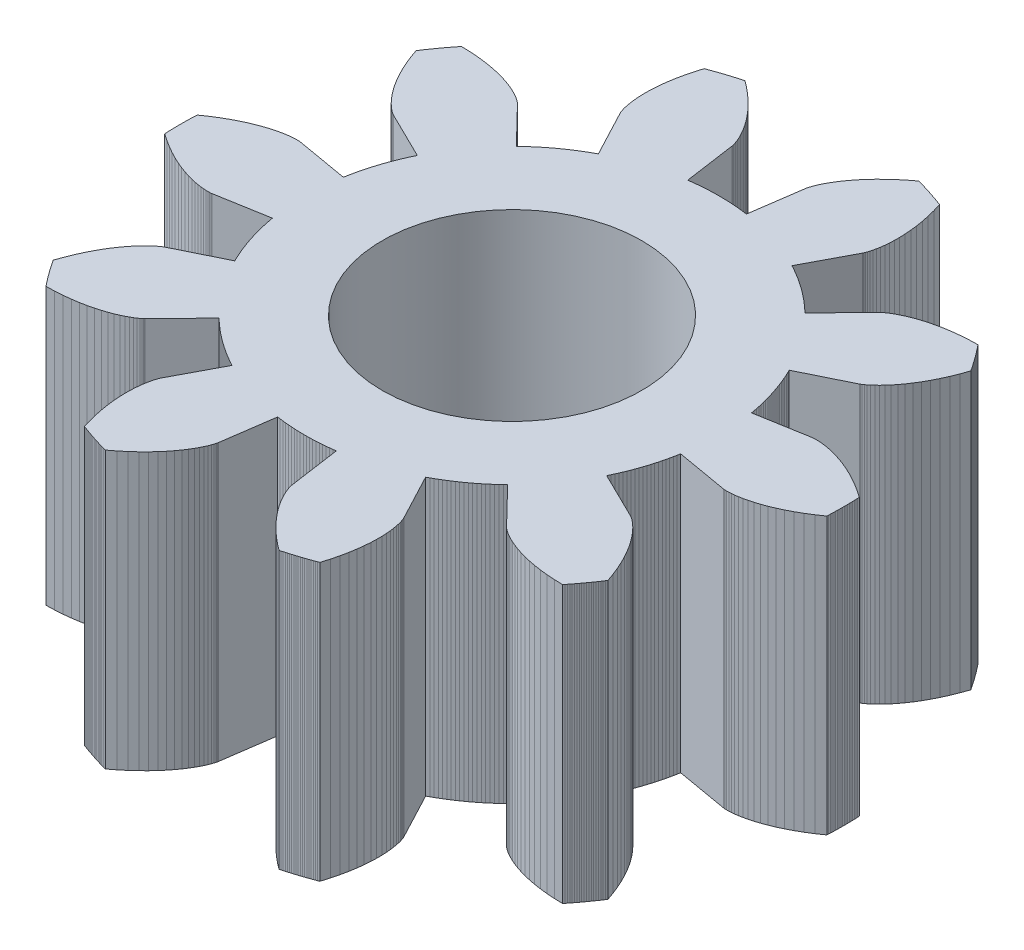
SolidWorks part; units mm, degrees
ref_plane "Front Plane" through (0, 0, 0) normal (0, 0, 1) x (1, 0, 0)
ref_plane "Top Plane" through (0, 0, 0) normal (0, 1, 0) x (1, 0, 0)
ref_plane "Right Plane" through (0, 0, 0) normal (1, 0, 0) x (0, 0, -1)
sketch "Sketch1" plane through (0, 0, 0) normal (0, 1, 0) x (1, 0, 0)
  line L0 (3.6947, -0.6418) -> (4.6291, -0.8041)
  line L1 (4.6291, -0.8041) -> (4.6332, -0.8047)
  line L2 (4.6332, -0.8047) -> (4.6455, -0.806)
  line L3 (4.6455, -0.806) -> (4.6659, -0.8073)
  line L4 (4.6659, -0.8073) -> (4.6947, -0.8081)
  line L5 (4.6947, -0.8081) -> (4.7316, -0.8074)
  line L6 (4.7316, -0.8074) -> (4.7767, -0.8048)
  line L7 (4.7767, -0.8048) -> (4.8297, -0.7994)
  line L8 (4.8297, -0.7994) -> (4.8907, -0.7907)
  line L9 (4.8907, -0.7907) -> (4.9593, -0.778)
  line L10 (4.9593, -0.778) -> (5.0353, -0.7605)
  line L11 (5.0353, -0.7605) -> (5.1184, -0.7378)
  line L12 (5.1184, -0.7378) -> (5.2084, -0.7091)
  line L13 (5.2084, -0.7091) -> (5.3047, -0.6738)
  line L14 (5.3047, -0.6738) -> (5.4071, -0.6314)
  line L15 (5.4071, -0.6314) -> (5.5151, -0.5813)
  line L16 (5.5151, -0.5813) -> (5.6282, -0.523)
  line L17 (5.6282, -0.523) -> (5.7459, -0.456)
  line L18 (5.7459, -0.456) -> (5.8676, -0.3797)
  line L19 (5.8676, -0.3797) -> (5.9928, -0.2937)
  line L20 (5.9928, -0.2937) -> (5.9942, -0.2628)
  line L21 (5.9942, -0.2628) -> (5.9955, -0.2319)
  line L22 (5.9955, -0.2319) -> (5.9966, -0.201)
  line L23 (5.9966, -0.201) -> (5.9976, -0.1701)
  line L24 (5.9976, -0.1701) -> (5.9984, -0.1392)
  line L25 (5.9984, -0.1392) -> (5.999, -0.1083)
  line L26 (5.999, -0.1083) -> (5.9995, -0.0773)
  line L27 (5.9995, -0.0773) -> (5.9998, -0.0464)
  line L28 (5.9998, -0.0464) -> (6, -0.0155)
  line L29 (6, -0.0155) -> (6, 0.0155)
  line L30 (6, 0.0155) -> (5.9998, 0.0464)
  line L31 (5.9998, 0.0464) -> (5.9995, 0.0773)
  line L32 (5.9995, 0.0773) -> (5.999, 0.1083)
  line L33 (5.999, 0.1083) -> (5.9984, 0.1392)
  line L34 (5.9984, 0.1392) -> (5.9976, 0.1701)
  line L35 (5.9976, 0.1701) -> (5.9966, 0.201)
  line L36 (5.9966, 0.201) -> (5.9955, 0.2319)
  line L37 (5.9955, 0.2319) -> (5.9942, 0.2628)
  line L38 (5.9942, 0.2628) -> (5.9928, 0.2937)
  line L39 (5.9928, 0.2937) -> (5.8676, 0.3797)
  line L40 (5.8676, 0.3797) -> (5.7459, 0.456)
  line L41 (5.7459, 0.456) -> (5.6282, 0.523)
  line L42 (5.6282, 0.523) -> (5.5151, 0.5813)
  line L43 (5.5151, 0.5813) -> (5.4071, 0.6314)
  line L44 (5.4071, 0.6314) -> (5.3047, 0.6738)
  line L45 (5.3047, 0.6738) -> (5.2084, 0.7091)
  line L46 (5.2084, 0.7091) -> (5.1184, 0.7378)
  line L47 (5.1184, 0.7378) -> (5.0353, 0.7605)
  line L48 (5.0353, 0.7605) -> (4.9593, 0.778)
  line L49 (4.9593, 0.778) -> (4.8907, 0.7907)
  line L50 (4.8907, 0.7907) -> (4.8297, 0.7994)
  line L51 (4.8297, 0.7994) -> (4.7767, 0.8048)
  line L52 (4.7767, 0.8048) -> (4.7316, 0.8074)
  line L53 (4.7316, 0.8074) -> (4.6947, 0.8081)
  line L54 (4.6947, 0.8081) -> (4.6659, 0.8073)
  line L55 (4.6659, 0.8073) -> (4.6455, 0.806)
  line L56 (4.6455, 0.806) -> (4.6332, 0.8047)
  line L57 (4.6332, 0.8047) -> (4.6291, 0.8041)
  line L58 (4.6291, 0.8041) -> (3.6947, 0.6418)
  line L59 (3.6947, 0.6418) -> (3.6847, 0.697)
  line L60 (3.6847, 0.697) -> (3.6738, 0.752)
  line L61 (3.6738, 0.752) -> (3.6621, 0.8069)
  line L62 (3.6621, 0.8069) -> (3.6497, 0.8617)
  line L63 (3.6497, 0.8617) -> (3.6364, 0.9162)
  line L64 (3.6364, 0.9162) -> (3.6222, 0.9705)
  line L65 (3.6222, 0.9705) -> (3.6073, 1.0246)
  line L66 (3.6073, 1.0246) -> (3.5916, 1.0785)
  line L67 (3.5916, 1.0785) -> (3.575, 1.1321)
  line L68 (3.575, 1.1321) -> (3.5577, 1.1855)
  line L69 (3.5577, 1.1855) -> (3.5396, 1.2386)
  line L70 (3.5396, 1.2386) -> (3.5206, 1.2914)
  line L71 (3.5206, 1.2914) -> (3.5009, 1.344)
  line L72 (3.5009, 1.344) -> (3.4804, 1.3962)
  line L73 (3.4804, 1.3962) -> (3.4591, 1.4481)
  line L74 (3.4591, 1.4481) -> (3.4371, 1.4997)
  line L75 (3.4371, 1.4997) -> (3.4142, 1.551)
  line L76 (3.4142, 1.551) -> (3.3906, 1.6019)
  line L77 (3.3906, 1.6019) -> (3.3663, 1.6525)
  line L78 (3.3663, 1.6525) -> (4.2177, 2.0704)
  line L79 (4.2177, 2.0704) -> (4.2213, 2.0723)
  line L80 (4.2213, 2.0723) -> (4.232, 2.0785)
  line L81 (4.232, 2.0785) -> (4.2494, 2.0894)
  line L82 (4.2494, 2.0894) -> (4.273, 2.1057)
  line L83 (4.273, 2.1057) -> (4.3025, 2.1279)
  line L84 (4.3025, 2.1279) -> (4.3374, 2.1566)
  line L85 (4.3374, 2.1566) -> (4.3773, 2.1921)
  line L86 (4.3773, 2.1921) -> (4.4214, 2.235)
  line L87 (4.4214, 2.235) -> (4.4694, 2.2856)
  line L88 (4.4694, 2.2856) -> (4.5207, 2.3444)
  line L89 (4.5207, 2.3444) -> (4.5746, 2.4117)
  line L90 (4.5746, 2.4117) -> (4.6304, 2.4877)
  line L91 (4.6304, 2.4877) -> (4.6877, 2.5729)
  line L92 (4.6877, 2.5729) -> (4.7456, 2.6674)
  line L93 (4.7456, 2.6674) -> (4.8035, 2.7714)
  line L94 (4.8035, 2.7714) -> (4.8607, 2.885)
  line L95 (4.8607, 2.885) -> (4.9165, 3.0085)
  line L96 (4.9165, 3.0085) -> (4.9702, 3.1417)
  line L97 (4.9702, 3.1417) -> (5.0209, 3.2848)
  line L98 (5.0209, 3.2848) -> (5.0039, 3.3107)
  line L99 (5.0039, 3.3107) -> (4.9868, 3.3364)
  line L100 (4.9868, 3.3364) -> (4.9695, 3.3621)
  line L101 (4.9695, 3.3621) -> (4.9521, 3.3877)
  line L102 (4.9521, 3.3877) -> (4.9346, 3.4132)
  line L103 (4.9346, 3.4132) -> (4.9169, 3.4386)
  line L104 (4.9169, 3.4386) -> (4.8992, 3.4639)
  line L105 (4.8992, 3.4639) -> (4.8812, 3.4891)
  line L106 (4.8812, 3.4891) -> (4.8632, 3.5142)
  line L107 (4.8632, 3.5142) -> (4.845, 3.5392)
  line L108 (4.845, 3.5392) -> (4.8267, 3.5641)
  line L109 (4.8267, 3.5641) -> (4.8082, 3.589)
  line L110 (4.8082, 3.589) -> (4.7897, 3.6137)
  line L111 (4.7897, 3.6137) -> (4.771, 3.6384)
  line L112 (4.771, 3.6384) -> (4.7522, 3.6629)
  line L113 (4.7522, 3.6629) -> (4.7332, 3.6874)
  line L114 (4.7332, 3.6874) -> (4.7141, 3.7117)
  line L115 (4.7141, 3.7117) -> (4.6949, 3.736)
  line L116 (4.6949, 3.736) -> (4.6756, 3.7601)
  line L117 (4.6756, 3.7601) -> (4.5238, 3.7561)
  line L118 (4.5238, 3.7561) -> (4.3805, 3.7462)
  line L119 (4.3805, 3.7462) -> (4.2459, 3.7313)
  line L120 (4.2459, 3.7313) -> (4.1201, 3.712)
  line L121 (4.1201, 3.712) -> (4.0033, 3.6891)
  line L122 (4.0033, 3.6891) -> (3.8956, 3.6632)
  line L123 (3.8956, 3.6632) -> (3.7969, 3.6351)
  line L124 (3.7969, 3.6351) -> (3.7072, 3.6054)
  line L125 (3.7072, 3.6054) -> (3.6266, 3.575)
  line L126 (3.6266, 3.575) -> (3.5549, 3.5444)
  line L127 (3.5549, 3.5444) -> (3.4919, 3.5144)
  line L128 (3.4919, 3.5144) -> (3.4374, 3.4856)
  line L129 (3.4374, 3.4856) -> (3.3914, 3.4587)
  line L130 (3.3914, 3.4587) -> (3.3533, 3.4344)
  line L131 (3.3533, 3.4344) -> (3.3231, 3.4132)
  line L132 (3.3231, 3.4132) -> (3.3003, 3.3957)
  line L133 (3.3003, 3.3957) -> (3.2845, 3.3826)
  line L134 (3.2845, 3.3826) -> (3.2754, 3.3743)
  line L135 (3.2754, 3.3743) -> (3.2724, 3.3715)
  line L136 (3.2724, 3.3715) -> (2.6118, 2.6909)
  line L137 (2.6118, 2.6909) -> (2.5713, 2.7297)
  line L138 (2.5713, 2.7297) -> (2.5301, 2.7678)
  line L139 (2.5301, 2.7678) -> (2.4884, 2.8054)
  line L140 (2.4884, 2.8054) -> (2.4462, 2.8423)
  line L141 (2.4462, 2.8423) -> (2.4034, 2.8786)
  line L142 (2.4034, 2.8786) -> (2.36, 2.9142)
  line L143 (2.36, 2.9142) -> (2.3161, 2.9492)
  line L144 (2.3161, 2.9492) -> (2.2717, 2.9836)
  line L145 (2.2717, 2.9836) -> (2.2268, 3.0172)
  line L146 (2.2268, 3.0172) -> (2.1814, 3.0502)
  line L147 (2.1814, 3.0502) -> (2.1355, 3.0825)
  line L148 (2.1355, 3.0825) -> (2.0892, 3.1141)
  line L149 (2.0892, 3.1141) -> (2.0423, 3.1451)
  line L150 (2.0423, 3.1451) -> (1.995, 3.1753)
  line L151 (1.995, 3.1753) -> (1.9473, 3.2048)
  line L152 (1.9473, 3.2048) -> (1.8991, 3.2336)
  line L153 (1.8991, 3.2336) -> (1.8505, 3.2616)
  line L154 (1.8505, 3.2616) -> (1.8015, 3.2889)
  line L155 (1.8015, 3.2889) -> (1.7521, 3.3155)
  line L156 (1.7521, 3.3155) -> (2.1952, 4.1541)
  line L157 (2.1952, 4.1541) -> (2.197, 4.1578)
  line L158 (2.197, 4.1578) -> (2.2021, 4.169)
  line L159 (2.2021, 4.169) -> (2.2097, 4.1881)
  line L160 (2.2097, 4.1881) -> (2.2192, 4.2152)
  line L161 (2.2192, 4.2152) -> (2.23, 4.2505)
  line L162 (2.23, 4.2505) -> (2.2415, 4.2942)
  line L163 (2.2415, 4.2942) -> (2.2528, 4.3463)
  line L164 (2.2528, 4.3463) -> (2.2633, 4.407)
  line L165 (2.2633, 4.407) -> (2.2724, 4.4762)
  line L166 (2.2724, 4.4762) -> (2.2793, 4.5538)
  line L167 (2.2793, 4.5538) -> (2.2834, 4.6399)
  line L168 (2.2834, 4.6399) -> (2.2838, 4.7343)
  line L169 (2.2838, 4.7343) -> (2.2801, 4.8369)
  line L170 (2.2801, 4.8369) -> (2.2714, 4.9474)
  line L171 (2.2714, 4.9474) -> (2.2571, 5.0655)
  line L172 (2.2571, 5.0655) -> (2.2366, 5.1911)
  line L173 (2.2366, 5.1911) -> (2.2092, 5.3237)
  line L174 (2.2092, 5.3237) -> (2.1743, 5.4631)
  line L175 (2.1743, 5.4631) -> (2.1312, 5.6087)
  line L176 (2.1312, 5.6087) -> (2.1023, 5.6196)
  line L177 (2.1023, 5.6196) -> (2.0733, 5.6304)
  line L178 (2.0733, 5.6304) -> (2.0442, 5.641)
  line L179 (2.0442, 5.641) -> (2.0151, 5.6515)
  line L180 (2.0151, 5.6515) -> (1.986, 5.6618)
  line L181 (1.986, 5.6618) -> (1.9568, 5.672)
  line L182 (1.9568, 5.672) -> (1.9275, 5.682)
  line L183 (1.9275, 5.682) -> (1.8982, 5.6918)
  line L184 (1.8982, 5.6918) -> (1.8688, 5.7015)
  line L185 (1.8688, 5.7015) -> (1.8394, 5.7111)
  line L186 (1.8394, 5.7111) -> (1.8099, 5.7205)
  line L187 (1.8099, 5.7205) -> (1.7804, 5.7298)
  line L188 (1.7804, 5.7298) -> (1.7508, 5.7389)
  line L189 (1.7508, 5.7389) -> (1.7212, 5.7478)
  line L190 (1.7212, 5.7478) -> (1.6916, 5.7566)
  line L191 (1.6916, 5.7566) -> (1.6619, 5.7653)
  line L192 (1.6619, 5.7653) -> (1.6321, 5.7737)
  line L193 (1.6321, 5.7737) -> (1.6023, 5.7821)
  line L194 (1.6023, 5.7821) -> (1.5725, 5.7903)
  line L195 (1.5725, 5.7903) -> (1.4521, 5.6977)
  line L196 (1.4521, 5.6977) -> (1.3419, 5.6055)
  line L197 (1.3419, 5.6055) -> (1.2418, 5.5143)
  line L198 (1.2418, 5.5143) -> (1.1514, 5.4248)
  line L199 (1.1514, 5.4248) -> (1.0704, 5.3376)
  line L200 (1.0704, 5.3376) -> (0.9984, 5.2533)
  line L201 (0.9984, 5.2533) -> (0.9351, 5.1726)
  line L202 (0.9351, 5.1726) -> (0.88, 5.0959)
  line L203 (0.88, 5.0959) -> (0.8327, 5.0239)
  line L204 (0.8327, 5.0239) -> (0.7926, 4.957)
  line L205 (0.7926, 4.957) -> (0.7593, 4.8957)
  line L206 (0.7593, 4.8957) -> (0.7322, 4.8404)
  line L207 (0.7322, 4.8404) -> (0.7107, 4.7916)
  line L208 (0.7107, 4.7916) -> (0.6942, 4.7495)
  line L209 (0.6942, 4.7495) -> (0.6822, 4.7146)
  line L210 (0.6822, 4.7146) -> (0.674, 4.687)
  line L211 (0.674, 4.687) -> (0.669, 4.6672)
  line L212 (0.669, 4.6672) -> (0.6665, 4.6551)
  line L213 (0.6665, 4.6551) -> (0.6658, 4.6511)
  line L214 (0.6658, 4.6511) -> (0.5314, 3.7122)
  line L215 (0.5314, 3.7122) -> (0.4757, 3.7197)
  line L216 (0.4757, 3.7197) -> (0.42, 3.7264)
  line L217 (0.42, 3.7264) -> (0.3642, 3.7323)
  line L218 (0.3642, 3.7323) -> (0.3083, 3.7373)
  line L219 (0.3083, 3.7373) -> (0.2524, 3.7415)
  line L220 (0.2524, 3.7415) -> (0.1963, 3.7449)
  line L221 (0.1963, 3.7449) -> (0.1403, 3.7474)
  line L222 (0.1403, 3.7474) -> (0.0842, 3.7491)
  line L223 (0.0842, 3.7491) -> (0.0281, 3.7499)
  line L224 (0.0281, 3.7499) -> (-0.0281, 3.7499)
  line L225 (-0.0281, 3.7499) -> (-0.0842, 3.7491)
  line L226 (-0.0842, 3.7491) -> (-0.1403, 3.7474)
  line L227 (-0.1403, 3.7474) -> (-0.1963, 3.7449)
  line L228 (-0.1963, 3.7449) -> (-0.2524, 3.7415)
  line L229 (-0.2524, 3.7415) -> (-0.3083, 3.7373)
  line L230 (-0.3083, 3.7373) -> (-0.3642, 3.7323)
  line L231 (-0.3642, 3.7323) -> (-0.42, 3.7264)
  line L232 (-0.42, 3.7264) -> (-0.4757, 3.7197)
  line L233 (-0.4757, 3.7197) -> (-0.5314, 3.7122)
  line L234 (-0.5314, 3.7122) -> (-0.6658, 4.6511)
  line L235 (-0.6658, 4.6511) -> (-0.6665, 4.6551)
  line L236 (-0.6665, 4.6551) -> (-0.669, 4.6672)
  line L237 (-0.669, 4.6672) -> (-0.674, 4.687)
  line L238 (-0.674, 4.687) -> (-0.6822, 4.7146)
  line L239 (-0.6822, 4.7146) -> (-0.6942, 4.7495)
  line L240 (-0.6942, 4.7495) -> (-0.7107, 4.7916)
  line L241 (-0.7107, 4.7916) -> (-0.7322, 4.8404)
  line L242 (-0.7322, 4.8404) -> (-0.7593, 4.8957)
  line L243 (-0.7593, 4.8957) -> (-0.7926, 4.957)
  line L244 (-0.7926, 4.957) -> (-0.8327, 5.0239)
  line L245 (-0.8327, 5.0239) -> (-0.88, 5.0959)
  line L246 (-0.88, 5.0959) -> (-0.9351, 5.1726)
  line L247 (-0.9351, 5.1726) -> (-0.9984, 5.2533)
  line L248 (-0.9984, 5.2533) -> (-1.0704, 5.3376)
  line L249 (-1.0704, 5.3376) -> (-1.1514, 5.4248)
  line L250 (-1.1514, 5.4248) -> (-1.2418, 5.5143)
  line L251 (-1.2418, 5.5143) -> (-1.3419, 5.6055)
  line L252 (-1.3419, 5.6055) -> (-1.4521, 5.6977)
  line L253 (-1.4521, 5.6977) -> (-1.5725, 5.7903)
  line L254 (-1.5725, 5.7903) -> (-1.6023, 5.7821)
  line L255 (-1.6023, 5.7821) -> (-1.6321, 5.7737)
  line L256 (-1.6321, 5.7737) -> (-1.6619, 5.7653)
  line L257 (-1.6619, 5.7653) -> (-1.6916, 5.7566)
  line L258 (-1.6916, 5.7566) -> (-1.7212, 5.7478)
  line L259 (-1.7212, 5.7478) -> (-1.7508, 5.7389)
  line L260 (-1.7508, 5.7389) -> (-1.7804, 5.7298)
  line L261 (-1.7804, 5.7298) -> (-1.8099, 5.7205)
  line L262 (-1.8099, 5.7205) -> (-1.8394, 5.7111)
  line L263 (-1.8394, 5.7111) -> (-1.8688, 5.7015)
  line L264 (-1.8688, 5.7015) -> (-1.8982, 5.6918)
  line L265 (-1.8982, 5.6918) -> (-1.9275, 5.682)
  line L266 (-1.9275, 5.682) -> (-1.9568, 5.672)
  line L267 (-1.9568, 5.672) -> (-1.986, 5.6618)
  line L268 (-1.986, 5.6618) -> (-2.0151, 5.6515)
  line L269 (-2.0151, 5.6515) -> (-2.0442, 5.641)
  line L270 (-2.0442, 5.641) -> (-2.0733, 5.6304)
  line L271 (-2.0733, 5.6304) -> (-2.1023, 5.6196)
  line L272 (-2.1023, 5.6196) -> (-2.1312, 5.6087)
  line L273 (-2.1312, 5.6087) -> (-2.1743, 5.4631)
  line L274 (-2.1743, 5.4631) -> (-2.2092, 5.3237)
  line L275 (-2.2092, 5.3237) -> (-2.2366, 5.1911)
  line L276 (-2.2366, 5.1911) -> (-2.2571, 5.0655)
  line L277 (-2.2571, 5.0655) -> (-2.2714, 4.9474)
  line L278 (-2.2714, 4.9474) -> (-2.2801, 4.8369)
  line L279 (-2.2801, 4.8369) -> (-2.2838, 4.7343)
  line L280 (-2.2838, 4.7343) -> (-2.2834, 4.6399)
  line L281 (-2.2834, 4.6399) -> (-2.2793, 4.5538)
  line L282 (-2.2793, 4.5538) -> (-2.2724, 4.4762)
  line L283 (-2.2724, 4.4762) -> (-2.2633, 4.407)
  line L284 (-2.2633, 4.407) -> (-2.2528, 4.3463)
  line L285 (-2.2528, 4.3463) -> (-2.2415, 4.2942)
  line L286 (-2.2415, 4.2942) -> (-2.23, 4.2505)
  line L287 (-2.23, 4.2505) -> (-2.2192, 4.2152)
  line L288 (-2.2192, 4.2152) -> (-2.2097, 4.1881)
  line L289 (-2.2097, 4.1881) -> (-2.2021, 4.169)
  line L290 (-2.2021, 4.169) -> (-2.197, 4.1578)
  line L291 (-2.197, 4.1578) -> (-2.1952, 4.1541)
  line L292 (-2.1952, 4.1541) -> (-1.7521, 3.3155)
  line L293 (-1.7521, 3.3155) -> (-1.8015, 3.2889)
  line L294 (-1.8015, 3.2889) -> (-1.8505, 3.2616)
  line L295 (-1.8505, 3.2616) -> (-1.8991, 3.2336)
  line L296 (-1.8991, 3.2336) -> (-1.9473, 3.2048)
  line L297 (-1.9473, 3.2048) -> (-1.995, 3.1753)
  line L298 (-1.995, 3.1753) -> (-2.0423, 3.1451)
  line L299 (-2.0423, 3.1451) -> (-2.0892, 3.1141)
  line L300 (-2.0892, 3.1141) -> (-2.1355, 3.0825)
  line L301 (-2.1355, 3.0825) -> (-2.1814, 3.0502)
  line L302 (-2.1814, 3.0502) -> (-2.2268, 3.0172)
  line L303 (-2.2268, 3.0172) -> (-2.2717, 2.9836)
  line L304 (-2.2717, 2.9836) -> (-2.3161, 2.9492)
  line L305 (-2.3161, 2.9492) -> (-2.36, 2.9142)
  line L306 (-2.36, 2.9142) -> (-2.4034, 2.8786)
  line L307 (-2.4034, 2.8786) -> (-2.4462, 2.8423)
  line L308 (-2.4462, 2.8423) -> (-2.4884, 2.8054)
  line L309 (-2.4884, 2.8054) -> (-2.5301, 2.7678)
  line L310 (-2.5301, 2.7678) -> (-2.5713, 2.7297)
  line L311 (-2.5713, 2.7297) -> (-2.6118, 2.6909)
  line L312 (-2.6118, 2.6909) -> (-3.2724, 3.3715)
  line L313 (-3.2724, 3.3715) -> (-3.2754, 3.3743)
  line L314 (-3.2754, 3.3743) -> (-3.2845, 3.3826)
  line L315 (-3.2845, 3.3826) -> (-3.3003, 3.3957)
  line L316 (-3.3003, 3.3957) -> (-3.3231, 3.4132)
  line L317 (-3.3231, 3.4132) -> (-3.3533, 3.4344)
  line L318 (-3.3533, 3.4344) -> (-3.3914, 3.4587)
  line L319 (-3.3914, 3.4587) -> (-3.4374, 3.4856)
  line L320 (-3.4374, 3.4856) -> (-3.4919, 3.5144)
  line L321 (-3.4919, 3.5144) -> (-3.5549, 3.5444)
  line L322 (-3.5549, 3.5444) -> (-3.6266, 3.575)
  line L323 (-3.6266, 3.575) -> (-3.7072, 3.6054)
  line L324 (-3.7072, 3.6054) -> (-3.7969, 3.6351)
  line L325 (-3.7969, 3.6351) -> (-3.8956, 3.6632)
  line L326 (-3.8956, 3.6632) -> (-4.0033, 3.6891)
  line L327 (-4.0033, 3.6891) -> (-4.1201, 3.712)
  line L328 (-4.1201, 3.712) -> (-4.2459, 3.7313)
  line L329 (-4.2459, 3.7313) -> (-4.3805, 3.7462)
  line L330 (-4.3805, 3.7462) -> (-4.5238, 3.7561)
  line L331 (-4.5238, 3.7561) -> (-4.6756, 3.7601)
  line L332 (-4.6756, 3.7601) -> (-4.6949, 3.736)
  line L333 (-4.6949, 3.736) -> (-4.7141, 3.7117)
  line L334 (-4.7141, 3.7117) -> (-4.7332, 3.6874)
  line L335 (-4.7332, 3.6874) -> (-4.7522, 3.6629)
  line L336 (-4.7522, 3.6629) -> (-4.771, 3.6384)
  line L337 (-4.771, 3.6384) -> (-4.7897, 3.6137)
  line L338 (-4.7897, 3.6137) -> (-4.8082, 3.589)
  line L339 (-4.8082, 3.589) -> (-4.8267, 3.5641)
  line L340 (-4.8267, 3.5641) -> (-4.845, 3.5392)
  line L341 (-4.845, 3.5392) -> (-4.8632, 3.5142)
  line L342 (-4.8632, 3.5142) -> (-4.8812, 3.4891)
  line L343 (-4.8812, 3.4891) -> (-4.8992, 3.4639)
  line L344 (-4.8992, 3.4639) -> (-4.9169, 3.4386)
  line L345 (-4.9169, 3.4386) -> (-4.9346, 3.4132)
  line L346 (-4.9346, 3.4132) -> (-4.9521, 3.3877)
  line L347 (-4.9521, 3.3877) -> (-4.9695, 3.3621)
  line L348 (-4.9695, 3.3621) -> (-4.9868, 3.3364)
  line L349 (-4.9868, 3.3364) -> (-5.0039, 3.3107)
  line L350 (-5.0039, 3.3107) -> (-5.0209, 3.2848)
  line L351 (-5.0209, 3.2848) -> (-4.9702, 3.1417)
  line L352 (-4.9702, 3.1417) -> (-4.9165, 3.0085)
  line L353 (-4.9165, 3.0085) -> (-4.8607, 2.885)
  line L354 (-4.8607, 2.885) -> (-4.8035, 2.7714)
  line L355 (-4.8035, 2.7714) -> (-4.7456, 2.6674)
  line L356 (-4.7456, 2.6674) -> (-4.6877, 2.5729)
  line L357 (-4.6877, 2.5729) -> (-4.6304, 2.4877)
  line L358 (-4.6304, 2.4877) -> (-4.5746, 2.4117)
  line L359 (-4.5746, 2.4117) -> (-4.5207, 2.3444)
  line L360 (-4.5207, 2.3444) -> (-4.4694, 2.2856)
  line L361 (-4.4694, 2.2856) -> (-4.4214, 2.235)
  line L362 (-4.4214, 2.235) -> (-4.3773, 2.1921)
  line L363 (-4.3773, 2.1921) -> (-4.3374, 2.1566)
  line L364 (-4.3374, 2.1566) -> (-4.3025, 2.1279)
  line L365 (-4.3025, 2.1279) -> (-4.273, 2.1057)
  line L366 (-4.273, 2.1057) -> (-4.2494, 2.0894)
  line L367 (-4.2494, 2.0894) -> (-4.232, 2.0785)
  line L368 (-4.232, 2.0785) -> (-4.2213, 2.0723)
  line L369 (-4.2213, 2.0723) -> (-4.2177, 2.0704)
  line L370 (-4.2177, 2.0704) -> (-3.3663, 1.6525)
  line L371 (-3.3663, 1.6525) -> (-3.3906, 1.6019)
  line L372 (-3.3906, 1.6019) -> (-3.4142, 1.551)
  line L373 (-3.4142, 1.551) -> (-3.4371, 1.4997)
  line L374 (-3.4371, 1.4997) -> (-3.4591, 1.4481)
  line L375 (-3.4591, 1.4481) -> (-3.4804, 1.3962)
  line L376 (-3.4804, 1.3962) -> (-3.5009, 1.344)
  line L377 (-3.5009, 1.344) -> (-3.5206, 1.2914)
  line L378 (-3.5206, 1.2914) -> (-3.5396, 1.2386)
  line L379 (-3.5396, 1.2386) -> (-3.5577, 1.1855)
  line L380 (-3.5577, 1.1855) -> (-3.575, 1.1321)
  line L381 (-3.575, 1.1321) -> (-3.5916, 1.0785)
  line L382 (-3.5916, 1.0785) -> (-3.6073, 1.0246)
  line L383 (-3.6073, 1.0246) -> (-3.6222, 0.9705)
  line L384 (-3.6222, 0.9705) -> (-3.6364, 0.9162)
  line L385 (-3.6364, 0.9162) -> (-3.6497, 0.8617)
  line L386 (-3.6497, 0.8617) -> (-3.6621, 0.8069)
  line L387 (-3.6621, 0.8069) -> (-3.6738, 0.752)
  line L388 (-3.6738, 0.752) -> (-3.6847, 0.697)
  line L389 (-3.6847, 0.697) -> (-3.6947, 0.6418)
  line L390 (-3.6947, 0.6418) -> (-4.6291, 0.8041)
  line L391 (-4.6291, 0.8041) -> (-4.6332, 0.8047)
  line L392 (-4.6332, 0.8047) -> (-4.6455, 0.806)
  line L393 (-4.6455, 0.806) -> (-4.6659, 0.8073)
  line L394 (-4.6659, 0.8073) -> (-4.6947, 0.8081)
  line L395 (-4.6947, 0.8081) -> (-4.7316, 0.8074)
  line L396 (-4.7316, 0.8074) -> (-4.7767, 0.8048)
  line L397 (-4.7767, 0.8048) -> (-4.8297, 0.7994)
  line L398 (-4.8297, 0.7994) -> (-4.8907, 0.7907)
  line L399 (-4.8907, 0.7907) -> (-4.9593, 0.778)
  line L400 (-4.9593, 0.778) -> (-5.0353, 0.7605)
  line L401 (-5.0353, 0.7605) -> (-5.1184, 0.7378)
  line L402 (-5.1184, 0.7378) -> (-5.2084, 0.7091)
  line L403 (-5.2084, 0.7091) -> (-5.3047, 0.6738)
  line L404 (-5.3047, 0.6738) -> (-5.4071, 0.6314)
  line L405 (-5.4071, 0.6314) -> (-5.5151, 0.5813)
  line L406 (-5.5151, 0.5813) -> (-5.6282, 0.523)
  line L407 (-5.6282, 0.523) -> (-5.7459, 0.456)
  line L408 (-5.7459, 0.456) -> (-5.8676, 0.3797)
  line L409 (-5.8676, 0.3797) -> (-5.9928, 0.2937)
  line L410 (-5.9928, 0.2937) -> (-5.9942, 0.2628)
  line L411 (-5.9942, 0.2628) -> (-5.9955, 0.2319)
  line L412 (-5.9955, 0.2319) -> (-5.9966, 0.201)
  line L413 (-5.9966, 0.201) -> (-5.9976, 0.1701)
  line L414 (-5.9976, 0.1701) -> (-5.9984, 0.1392)
  line L415 (-5.9984, 0.1392) -> (-5.999, 0.1083)
  line L416 (-5.999, 0.1083) -> (-5.9995, 0.0773)
  line L417 (-5.9995, 0.0773) -> (-5.9998, 0.0464)
  line L418 (-5.9998, 0.0464) -> (-6, 0.0155)
  line L419 (-6, 0.0155) -> (-6, -0.0155)
  line L420 (-6, -0.0155) -> (-5.9998, -0.0464)
  line L421 (-5.9998, -0.0464) -> (-5.9995, -0.0773)
  line L422 (-5.9995, -0.0773) -> (-5.999, -0.1083)
  line L423 (-5.999, -0.1083) -> (-5.9984, -0.1392)
  line L424 (-5.9984, -0.1392) -> (-5.9976, -0.1701)
  line L425 (-5.9976, -0.1701) -> (-5.9966, -0.201)
  line L426 (-5.9966, -0.201) -> (-5.9955, -0.2319)
  line L427 (-5.9955, -0.2319) -> (-5.9942, -0.2628)
  line L428 (-5.9942, -0.2628) -> (-5.9928, -0.2937)
  line L429 (-5.9928, -0.2937) -> (-5.8676, -0.3797)
  line L430 (-5.8676, -0.3797) -> (-5.7459, -0.456)
  line L431 (-5.7459, -0.456) -> (-5.6282, -0.523)
  line L432 (-5.6282, -0.523) -> (-5.5151, -0.5813)
  line L433 (-5.5151, -0.5813) -> (-5.4071, -0.6314)
  line L434 (-5.4071, -0.6314) -> (-5.3047, -0.6738)
  line L435 (-5.3047, -0.6738) -> (-5.2084, -0.7091)
  line L436 (-5.2084, -0.7091) -> (-5.1184, -0.7378)
  line L437 (-5.1184, -0.7378) -> (-5.0353, -0.7605)
  line L438 (-5.0353, -0.7605) -> (-4.9593, -0.778)
  line L439 (-4.9593, -0.778) -> (-4.8907, -0.7907)
  line L440 (-4.8907, -0.7907) -> (-4.8297, -0.7994)
  line L441 (-4.8297, -0.7994) -> (-4.7767, -0.8048)
  line L442 (-4.7767, -0.8048) -> (-4.7316, -0.8074)
  line L443 (-4.7316, -0.8074) -> (-4.6947, -0.8081)
  line L444 (-4.6947, -0.8081) -> (-4.6659, -0.8073)
  line L445 (-4.6659, -0.8073) -> (-4.6455, -0.806)
  line L446 (-4.6455, -0.806) -> (-4.6332, -0.8047)
  line L447 (-4.6332, -0.8047) -> (-4.6291, -0.8041)
  line L448 (-4.6291, -0.8041) -> (-3.6947, -0.6418)
  line L449 (-3.6947, -0.6418) -> (-3.6847, -0.697)
  line L450 (-3.6847, -0.697) -> (-3.6738, -0.752)
  line L451 (-3.6738, -0.752) -> (-3.6621, -0.8069)
  line L452 (-3.6621, -0.8069) -> (-3.6497, -0.8617)
  line L453 (-3.6497, -0.8617) -> (-3.6364, -0.9162)
  line L454 (-3.6364, -0.9162) -> (-3.6222, -0.9705)
  line L455 (-3.6222, -0.9705) -> (-3.6073, -1.0246)
  line L456 (-3.6073, -1.0246) -> (-3.5916, -1.0785)
  line L457 (-3.5916, -1.0785) -> (-3.575, -1.1321)
  line L458 (-3.575, -1.1321) -> (-3.5577, -1.1855)
  line L459 (-3.5577, -1.1855) -> (-3.5396, -1.2386)
  line L460 (-3.5396, -1.2386) -> (-3.5206, -1.2914)
  line L461 (-3.5206, -1.2914) -> (-3.5009, -1.344)
  line L462 (-3.5009, -1.344) -> (-3.4804, -1.3962)
  line L463 (-3.4804, -1.3962) -> (-3.4591, -1.4481)
  line L464 (-3.4591, -1.4481) -> (-3.4371, -1.4997)
  line L465 (-3.4371, -1.4997) -> (-3.4142, -1.551)
  line L466 (-3.4142, -1.551) -> (-3.3906, -1.6019)
  line L467 (-3.3906, -1.6019) -> (-3.3663, -1.6525)
  line L468 (-3.3663, -1.6525) -> (-4.2177, -2.0704)
  line L469 (-4.2177, -2.0704) -> (-4.2213, -2.0723)
  line L470 (-4.2213, -2.0723) -> (-4.232, -2.0785)
  line L471 (-4.232, -2.0785) -> (-4.2494, -2.0894)
  line L472 (-4.2494, -2.0894) -> (-4.273, -2.1057)
  line L473 (-4.273, -2.1057) -> (-4.3025, -2.1279)
  line L474 (-4.3025, -2.1279) -> (-4.3374, -2.1566)
  line L475 (-4.3374, -2.1566) -> (-4.3773, -2.1921)
  line L476 (-4.3773, -2.1921) -> (-4.4214, -2.235)
  line L477 (-4.4214, -2.235) -> (-4.4694, -2.2856)
  line L478 (-4.4694, -2.2856) -> (-4.5207, -2.3444)
  line L479 (-4.5207, -2.3444) -> (-4.5746, -2.4117)
  line L480 (-4.5746, -2.4117) -> (-4.6304, -2.4877)
  line L481 (-4.6304, -2.4877) -> (-4.6877, -2.5729)
  line L482 (-4.6877, -2.5729) -> (-4.7456, -2.6674)
  line L483 (-4.7456, -2.6674) -> (-4.8035, -2.7714)
  line L484 (-4.8035, -2.7714) -> (-4.8607, -2.885)
  line L485 (-4.8607, -2.885) -> (-4.9165, -3.0085)
  line L486 (-4.9165, -3.0085) -> (-4.9702, -3.1417)
  line L487 (-4.9702, -3.1417) -> (-5.0209, -3.2848)
  line L488 (-5.0209, -3.2848) -> (-5.0039, -3.3107)
  line L489 (-5.0039, -3.3107) -> (-4.9868, -3.3364)
  line L490 (-4.9868, -3.3364) -> (-4.9695, -3.3621)
  line L491 (-4.9695, -3.3621) -> (-4.9521, -3.3877)
  line L492 (-4.9521, -3.3877) -> (-4.9346, -3.4132)
  line L493 (-4.9346, -3.4132) -> (-4.9169, -3.4386)
  line L494 (-4.9169, -3.4386) -> (-4.8992, -3.4639)
  line L495 (-4.8992, -3.4639) -> (-4.8812, -3.4891)
  line L496 (-4.8812, -3.4891) -> (-4.8632, -3.5142)
  line L497 (-4.8632, -3.5142) -> (-4.845, -3.5392)
  line L498 (-4.845, -3.5392) -> (-4.8267, -3.5641)
  line L499 (-4.8267, -3.5641) -> (-4.8082, -3.589)
  line L500 (-4.8082, -3.589) -> (-4.7897, -3.6137)
  line L501 (-4.7897, -3.6137) -> (-4.771, -3.6384)
  line L502 (-4.771, -3.6384) -> (-4.7522, -3.6629)
  line L503 (-4.7522, -3.6629) -> (-4.7332, -3.6874)
  line L504 (-4.7332, -3.6874) -> (-4.7141, -3.7117)
  line L505 (-4.7141, -3.7117) -> (-4.6949, -3.736)
  line L506 (-4.6949, -3.736) -> (-4.6756, -3.7601)
  line L507 (-4.6756, -3.7601) -> (-4.5238, -3.7561)
  line L508 (-4.5238, -3.7561) -> (-4.3805, -3.7462)
  line L509 (-4.3805, -3.7462) -> (-4.2459, -3.7313)
  line L510 (-4.2459, -3.7313) -> (-4.1201, -3.712)
  line L511 (-4.1201, -3.712) -> (-4.0033, -3.6891)
  line L512 (-4.0033, -3.6891) -> (-3.8956, -3.6632)
  line L513 (-3.8956, -3.6632) -> (-3.7969, -3.6351)
  line L514 (-3.7969, -3.6351) -> (-3.7072, -3.6054)
  line L515 (-3.7072, -3.6054) -> (-3.6266, -3.575)
  line L516 (-3.6266, -3.575) -> (-3.5549, -3.5444)
  line L517 (-3.5549, -3.5444) -> (-3.4919, -3.5144)
  line L518 (-3.4919, -3.5144) -> (-3.4374, -3.4856)
  line L519 (-3.4374, -3.4856) -> (-3.3914, -3.4587)
  line L520 (-3.3914, -3.4587) -> (-3.3533, -3.4344)
  line L521 (-3.3533, -3.4344) -> (-3.3231, -3.4132)
  line L522 (-3.3231, -3.4132) -> (-3.3003, -3.3957)
  line L523 (-3.3003, -3.3957) -> (-3.2845, -3.3826)
  line L524 (-3.2845, -3.3826) -> (-3.2754, -3.3743)
  line L525 (-3.2754, -3.3743) -> (-3.2724, -3.3715)
  line L526 (-3.2724, -3.3715) -> (-2.6118, -2.6909)
  line L527 (-2.6118, -2.6909) -> (-2.5713, -2.7297)
  line L528 (-2.5713, -2.7297) -> (-2.5301, -2.7678)
  line L529 (-2.5301, -2.7678) -> (-2.4884, -2.8054)
  line L530 (-2.4884, -2.8054) -> (-2.4462, -2.8423)
  line L531 (-2.4462, -2.8423) -> (-2.4034, -2.8786)
  line L532 (-2.4034, -2.8786) -> (-2.36, -2.9142)
  line L533 (-2.36, -2.9142) -> (-2.3161, -2.9492)
  line L534 (-2.3161, -2.9492) -> (-2.2717, -2.9836)
  line L535 (-2.2717, -2.9836) -> (-2.2268, -3.0172)
  line L536 (-2.2268, -3.0172) -> (-2.1814, -3.0502)
  line L537 (-2.1814, -3.0502) -> (-2.1355, -3.0825)
  line L538 (-2.1355, -3.0825) -> (-2.0892, -3.1141)
  line L539 (-2.0892, -3.1141) -> (-2.0423, -3.1451)
  line L540 (-2.0423, -3.1451) -> (-1.995, -3.1753)
  line L541 (-1.995, -3.1753) -> (-1.9473, -3.2048)
  line L542 (-1.9473, -3.2048) -> (-1.8991, -3.2336)
  line L543 (-1.8991, -3.2336) -> (-1.8505, -3.2616)
  line L544 (-1.8505, -3.2616) -> (-1.8015, -3.2889)
  line L545 (-1.8015, -3.2889) -> (-1.7521, -3.3155)
  line L546 (-1.7521, -3.3155) -> (-2.1952, -4.1541)
  line L547 (-2.1952, -4.1541) -> (-2.197, -4.1578)
  line L548 (-2.197, -4.1578) -> (-2.2021, -4.169)
  line L549 (-2.2021, -4.169) -> (-2.2097, -4.1881)
  line L550 (-2.2097, -4.1881) -> (-2.2192, -4.2152)
  line L551 (-2.2192, -4.2152) -> (-2.23, -4.2505)
  line L552 (-2.23, -4.2505) -> (-2.2415, -4.2942)
  line L553 (-2.2415, -4.2942) -> (-2.2528, -4.3463)
  line L554 (-2.2528, -4.3463) -> (-2.2633, -4.407)
  line L555 (-2.2633, -4.407) -> (-2.2724, -4.4762)
  line L556 (-2.2724, -4.4762) -> (-2.2793, -4.5538)
  line L557 (-2.2793, -4.5538) -> (-2.2834, -4.6399)
  line L558 (-2.2834, -4.6399) -> (-2.2838, -4.7343)
  line L559 (-2.2838, -4.7343) -> (-2.2801, -4.8369)
  line L560 (-2.2801, -4.8369) -> (-2.2714, -4.9474)
  line L561 (-2.2714, -4.9474) -> (-2.2571, -5.0655)
  line L562 (-2.2571, -5.0655) -> (-2.2366, -5.1911)
  line L563 (-2.2366, -5.1911) -> (-2.2092, -5.3237)
  line L564 (-2.2092, -5.3237) -> (-2.1743, -5.4631)
  line L565 (-2.1743, -5.4631) -> (-2.1312, -5.6087)
  line L566 (-2.1312, -5.6087) -> (-2.1023, -5.6196)
  line L567 (-2.1023, -5.6196) -> (-2.0733, -5.6304)
  line L568 (-2.0733, -5.6304) -> (-2.0442, -5.641)
  line L569 (-2.0442, -5.641) -> (-2.0151, -5.6515)
  line L570 (-2.0151, -5.6515) -> (-1.986, -5.6618)
  line L571 (-1.986, -5.6618) -> (-1.9568, -5.672)
  line L572 (-1.9568, -5.672) -> (-1.9275, -5.682)
  line L573 (-1.9275, -5.682) -> (-1.8982, -5.6918)
  line L574 (-1.8982, -5.6918) -> (-1.8688, -5.7015)
  line L575 (-1.8688, -5.7015) -> (-1.8394, -5.7111)
  line L576 (-1.8394, -5.7111) -> (-1.8099, -5.7205)
  line L577 (-1.8099, -5.7205) -> (-1.7804, -5.7298)
  line L578 (-1.7804, -5.7298) -> (-1.7508, -5.7389)
  line L579 (-1.7508, -5.7389) -> (-1.7212, -5.7478)
  line L580 (-1.7212, -5.7478) -> (-1.6916, -5.7566)
  line L581 (-1.6916, -5.7566) -> (-1.6619, -5.7653)
  line L582 (-1.6619, -5.7653) -> (-1.6321, -5.7737)
  line L583 (-1.6321, -5.7737) -> (-1.6023, -5.7821)
  line L584 (-1.6023, -5.7821) -> (-1.5725, -5.7903)
  line L585 (-1.5725, -5.7903) -> (-1.4521, -5.6977)
  line L586 (-1.4521, -5.6977) -> (-1.3419, -5.6055)
  line L587 (-1.3419, -5.6055) -> (-1.2418, -5.5143)
  line L588 (-1.2418, -5.5143) -> (-1.1514, -5.4248)
  line L589 (-1.1514, -5.4248) -> (-1.0704, -5.3376)
  line L590 (-1.0704, -5.3376) -> (-0.9984, -5.2533)
  line L591 (-0.9984, -5.2533) -> (-0.9351, -5.1726)
  line L592 (-0.9351, -5.1726) -> (-0.88, -5.0959)
  line L593 (-0.88, -5.0959) -> (-0.8327, -5.0239)
  line L594 (-0.8327, -5.0239) -> (-0.7926, -4.957)
  line L595 (-0.7926, -4.957) -> (-0.7593, -4.8957)
  line L596 (-0.7593, -4.8957) -> (-0.7322, -4.8404)
  line L597 (-0.7322, -4.8404) -> (-0.7107, -4.7916)
  line L598 (-0.7107, -4.7916) -> (-0.6942, -4.7495)
  line L599 (-0.6942, -4.7495) -> (-0.6822, -4.7146)
  line L600 (-0.6822, -4.7146) -> (-0.674, -4.687)
  line L601 (-0.674, -4.687) -> (-0.669, -4.6672)
  line L602 (-0.669, -4.6672) -> (-0.6665, -4.6551)
  line L603 (-0.6665, -4.6551) -> (-0.6658, -4.6511)
  line L604 (-0.6658, -4.6511) -> (-0.5314, -3.7122)
  line L605 (-0.5314, -3.7122) -> (-0.4757, -3.7197)
  line L606 (-0.4757, -3.7197) -> (-0.42, -3.7264)
  line L607 (-0.42, -3.7264) -> (-0.3642, -3.7323)
  line L608 (-0.3642, -3.7323) -> (-0.3083, -3.7373)
  line L609 (-0.3083, -3.7373) -> (-0.2524, -3.7415)
  line L610 (-0.2524, -3.7415) -> (-0.1963, -3.7449)
  line L611 (-0.1963, -3.7449) -> (-0.1403, -3.7474)
  line L612 (-0.1403, -3.7474) -> (-0.0842, -3.7491)
  line L613 (-0.0842, -3.7491) -> (-0.0281, -3.7499)
  line L614 (-0.0281, -3.7499) -> (0.0281, -3.7499)
  line L615 (0.0281, -3.7499) -> (0.0842, -3.7491)
  line L616 (0.0842, -3.7491) -> (0.1403, -3.7474)
  line L617 (0.1403, -3.7474) -> (0.1963, -3.7449)
  line L618 (0.1963, -3.7449) -> (0.2524, -3.7415)
  line L619 (0.2524, -3.7415) -> (0.3083, -3.7373)
  line L620 (0.3083, -3.7373) -> (0.3642, -3.7323)
  line L621 (0.3642, -3.7323) -> (0.42, -3.7264)
  line L622 (0.42, -3.7264) -> (0.4757, -3.7197)
  line L623 (0.4757, -3.7197) -> (0.5314, -3.7122)
  line L624 (0.5314, -3.7122) -> (0.6658, -4.6511)
  line L625 (0.6658, -4.6511) -> (0.6665, -4.6551)
  line L626 (0.6665, -4.6551) -> (0.669, -4.6672)
  line L627 (0.669, -4.6672) -> (0.674, -4.687)
  line L628 (0.674, -4.687) -> (0.6822, -4.7146)
  line L629 (0.6822, -4.7146) -> (0.6942, -4.7495)
  line L630 (0.6942, -4.7495) -> (0.7107, -4.7916)
  line L631 (0.7107, -4.7916) -> (0.7322, -4.8404)
  line L632 (0.7322, -4.8404) -> (0.7593, -4.8957)
  line L633 (0.7593, -4.8957) -> (0.7926, -4.957)
  line L634 (0.7926, -4.957) -> (0.8327, -5.0239)
  line L635 (0.8327, -5.0239) -> (0.88, -5.0959)
  line L636 (0.88, -5.0959) -> (0.9351, -5.1726)
  line L637 (0.9351, -5.1726) -> (0.9984, -5.2533)
  line L638 (0.9984, -5.2533) -> (1.0704, -5.3376)
  line L639 (1.0704, -5.3376) -> (1.1514, -5.4248)
  line L640 (1.1514, -5.4248) -> (1.2418, -5.5143)
  line L641 (1.2418, -5.5143) -> (1.3419, -5.6055)
  line L642 (1.3419, -5.6055) -> (1.4521, -5.6977)
  line L643 (1.4521, -5.6977) -> (1.5725, -5.7903)
  line L644 (1.5725, -5.7903) -> (1.6023, -5.7821)
  line L645 (1.6023, -5.7821) -> (1.6321, -5.7737)
  line L646 (1.6321, -5.7737) -> (1.6619, -5.7653)
  line L647 (1.6619, -5.7653) -> (1.6916, -5.7566)
  line L648 (1.6916, -5.7566) -> (1.7212, -5.7478)
  line L649 (1.7212, -5.7478) -> (1.7508, -5.7389)
  line L650 (1.7508, -5.7389) -> (1.7804, -5.7298)
  line L651 (1.7804, -5.7298) -> (1.8099, -5.7205)
  line L652 (1.8099, -5.7205) -> (1.8394, -5.7111)
  line L653 (1.8394, -5.7111) -> (1.8688, -5.7015)
  line L654 (1.8688, -5.7015) -> (1.8982, -5.6918)
  line L655 (1.8982, -5.6918) -> (1.9275, -5.682)
  line L656 (1.9275, -5.682) -> (1.9568, -5.672)
  line L657 (1.9568, -5.672) -> (1.986, -5.6618)
  line L658 (1.986, -5.6618) -> (2.0151, -5.6515)
  line L659 (2.0151, -5.6515) -> (2.0442, -5.641)
  line L660 (2.0442, -5.641) -> (2.0733, -5.6304)
  line L661 (2.0733, -5.6304) -> (2.1023, -5.6196)
  line L662 (2.1023, -5.6196) -> (2.1312, -5.6087)
  line L663 (2.1312, -5.6087) -> (2.1743, -5.4631)
  line L664 (2.1743, -5.4631) -> (2.2092, -5.3237)
  line L665 (2.2092, -5.3237) -> (2.2366, -5.1911)
  line L666 (2.2366, -5.1911) -> (2.2571, -5.0655)
  line L667 (2.2571, -5.0655) -> (2.2714, -4.9474)
  line L668 (2.2714, -4.9474) -> (2.2801, -4.8369)
  line L669 (2.2801, -4.8369) -> (2.2838, -4.7343)
  line L670 (2.2838, -4.7343) -> (2.2834, -4.6399)
  line L671 (2.2834, -4.6399) -> (2.2793, -4.5538)
  line L672 (2.2793, -4.5538) -> (2.2724, -4.4762)
  line L673 (2.2724, -4.4762) -> (2.2633, -4.407)
  line L674 (2.2633, -4.407) -> (2.2528, -4.3463)
  line L675 (2.2528, -4.3463) -> (2.2415, -4.2942)
  line L676 (2.2415, -4.2942) -> (2.23, -4.2505)
  line L677 (2.23, -4.2505) -> (2.2192, -4.2152)
  line L678 (2.2192, -4.2152) -> (2.2097, -4.1881)
  line L679 (2.2097, -4.1881) -> (2.2021, -4.169)
  line L680 (2.2021, -4.169) -> (2.197, -4.1578)
  line L681 (2.197, -4.1578) -> (2.1952, -4.1541)
  line L682 (2.1952, -4.1541) -> (1.7521, -3.3155)
  line L683 (1.7521, -3.3155) -> (1.8015, -3.2889)
  line L684 (1.8015, -3.2889) -> (1.8505, -3.2616)
  line L685 (1.8505, -3.2616) -> (1.8991, -3.2336)
  line L686 (1.8991, -3.2336) -> (1.9473, -3.2048)
  line L687 (1.9473, -3.2048) -> (1.995, -3.1753)
  line L688 (1.995, -3.1753) -> (2.0423, -3.1451)
  line L689 (2.0423, -3.1451) -> (2.0892, -3.1141)
  line L690 (2.0892, -3.1141) -> (2.1355, -3.0825)
  line L691 (2.1355, -3.0825) -> (2.1814, -3.0502)
  line L692 (2.1814, -3.0502) -> (2.2268, -3.0172)
  line L693 (2.2268, -3.0172) -> (2.2717, -2.9836)
  line L694 (2.2717, -2.9836) -> (2.3161, -2.9492)
  line L695 (2.3161, -2.9492) -> (2.36, -2.9142)
  line L696 (2.36, -2.9142) -> (2.4034, -2.8786)
  line L697 (2.4034, -2.8786) -> (2.4462, -2.8423)
  line L698 (2.4462, -2.8423) -> (2.4884, -2.8054)
  line L699 (2.4884, -2.8054) -> (2.5301, -2.7678)
  line L700 (2.5301, -2.7678) -> (2.5713, -2.7297)
  line L701 (2.5713, -2.7297) -> (2.6118, -2.6909)
  line L702 (2.6118, -2.6909) -> (3.2724, -3.3715)
  line L703 (3.2724, -3.3715) -> (3.2754, -3.3743)
  line L704 (3.2754, -3.3743) -> (3.2845, -3.3826)
  line L705 (3.2845, -3.3826) -> (3.3003, -3.3957)
  line L706 (3.3003, -3.3957) -> (3.3231, -3.4132)
  line L707 (3.3231, -3.4132) -> (3.3533, -3.4344)
  line L708 (3.3533, -3.4344) -> (3.3914, -3.4587)
  line L709 (3.3914, -3.4587) -> (3.4374, -3.4856)
  line L710 (3.4374, -3.4856) -> (3.4919, -3.5144)
  line L711 (3.4919, -3.5144) -> (3.5549, -3.5444)
  line L712 (3.5549, -3.5444) -> (3.6266, -3.575)
  line L713 (3.6266, -3.575) -> (3.7072, -3.6054)
  line L714 (3.7072, -3.6054) -> (3.7969, -3.6351)
  line L715 (3.7969, -3.6351) -> (3.8956, -3.6632)
  line L716 (3.8956, -3.6632) -> (4.0033, -3.6891)
  line L717 (4.0033, -3.6891) -> (4.1201, -3.712)
  line L718 (4.1201, -3.712) -> (4.2459, -3.7313)
  line L719 (4.2459, -3.7313) -> (4.3805, -3.7462)
  line L720 (4.3805, -3.7462) -> (4.5238, -3.7561)
  line L721 (4.5238, -3.7561) -> (4.6756, -3.7601)
  line L722 (4.6756, -3.7601) -> (4.6949, -3.736)
  line L723 (4.6949, -3.736) -> (4.7141, -3.7117)
  line L724 (4.7141, -3.7117) -> (4.7332, -3.6874)
  line L725 (4.7332, -3.6874) -> (4.7522, -3.6629)
  line L726 (4.7522, -3.6629) -> (4.771, -3.6384)
  line L727 (4.771, -3.6384) -> (4.7897, -3.6137)
  line L728 (4.7897, -3.6137) -> (4.8082, -3.589)
  line L729 (4.8082, -3.589) -> (4.8267, -3.5641)
  line L730 (4.8267, -3.5641) -> (4.845, -3.5392)
  line L731 (4.845, -3.5392) -> (4.8632, -3.5142)
  line L732 (4.8632, -3.5142) -> (4.8812, -3.4891)
  line L733 (4.8812, -3.4891) -> (4.8992, -3.4639)
  line L734 (4.8992, -3.4639) -> (4.9169, -3.4386)
  line L735 (4.9169, -3.4386) -> (4.9346, -3.4132)
  line L736 (4.9346, -3.4132) -> (4.9521, -3.3877)
  line L737 (4.9521, -3.3877) -> (4.9695, -3.3621)
  line L738 (4.9695, -3.3621) -> (4.9868, -3.3364)
  line L739 (4.9868, -3.3364) -> (5.0039, -3.3107)
  line L740 (5.0039, -3.3107) -> (5.0209, -3.2848)
  line L741 (5.0209, -3.2848) -> (4.9702, -3.1417)
  line L742 (4.9702, -3.1417) -> (4.9165, -3.0085)
  line L743 (4.9165, -3.0085) -> (4.8607, -2.885)
  line L744 (4.8607, -2.885) -> (4.8035, -2.7714)
  line L745 (4.8035, -2.7714) -> (4.7456, -2.6674)
  line L746 (4.7456, -2.6674) -> (4.6877, -2.5729)
  line L747 (4.6877, -2.5729) -> (4.6304, -2.4877)
  line L748 (4.6304, -2.4877) -> (4.5746, -2.4117)
  line L749 (4.5746, -2.4117) -> (4.5207, -2.3444)
  line L750 (4.5207, -2.3444) -> (4.4694, -2.2856)
  line L751 (4.4694, -2.2856) -> (4.4214, -2.235)
  line L752 (4.4214, -2.235) -> (4.3773, -2.1921)
  line L753 (4.3773, -2.1921) -> (4.3374, -2.1566)
  line L754 (4.3374, -2.1566) -> (4.3025, -2.1279)
  line L755 (4.3025, -2.1279) -> (4.273, -2.1057)
  line L756 (4.273, -2.1057) -> (4.2494, -2.0894)
  line L757 (4.2494, -2.0894) -> (4.232, -2.0785)
  line L758 (4.232, -2.0785) -> (4.2213, -2.0723)
  line L759 (4.2213, -2.0723) -> (4.2177, -2.0704)
  line L760 (4.2177, -2.0704) -> (3.3663, -1.6525)
  line L761 (3.3663, -1.6525) -> (3.3906, -1.6019)
  line L762 (3.3906, -1.6019) -> (3.4142, -1.551)
  line L763 (3.4142, -1.551) -> (3.4371, -1.4997)
  line L764 (3.4371, -1.4997) -> (3.4591, -1.4481)
  line L765 (3.4591, -1.4481) -> (3.4804, -1.3962)
  line L766 (3.4804, -1.3962) -> (3.5009, -1.344)
  line L767 (3.5009, -1.344) -> (3.5206, -1.2914)
  line L768 (3.5206, -1.2914) -> (3.5396, -1.2386)
  line L769 (3.5396, -1.2386) -> (3.5577, -1.1855)
  line L770 (3.5577, -1.1855) -> (3.575, -1.1321)
  line L771 (3.575, -1.1321) -> (3.5916, -1.0785)
  line L772 (3.5916, -1.0785) -> (3.6073, -1.0246)
  line L773 (3.6073, -1.0246) -> (3.6222, -0.9705)
  line L774 (3.6222, -0.9705) -> (3.6364, -0.9162)
  line L775 (3.6364, -0.9162) -> (3.6497, -0.8617)
  line L776 (3.6497, -0.8617) -> (3.6621, -0.8069)
  line L777 (3.6621, -0.8069) -> (3.6738, -0.752)
  line L778 (3.6738, -0.752) -> (3.6847, -0.697)
  line L779 (3.6847, -0.697) -> (3.6947, -0.6418)
extrude "Boss-Extrude1" add sketch "Sketch1" along normal blind 5
sketch "Sketch2" plane through (0, 5, 0) normal (0, 1, 0) x (1, 0, 0)
  circle A0 centre (0, 0) radius 2.35
  dimension "D1" = 4.7
extrude "Cut-Extrude1" cut sketch "Sketch2" against normal through all
sketch "Sketch3" plane through (0, 5, 0) normal (0, 1, 0) x (1, 0, 0)
  circle A0 centre (0, 0) radius 5
  dimension "D1" = 10
